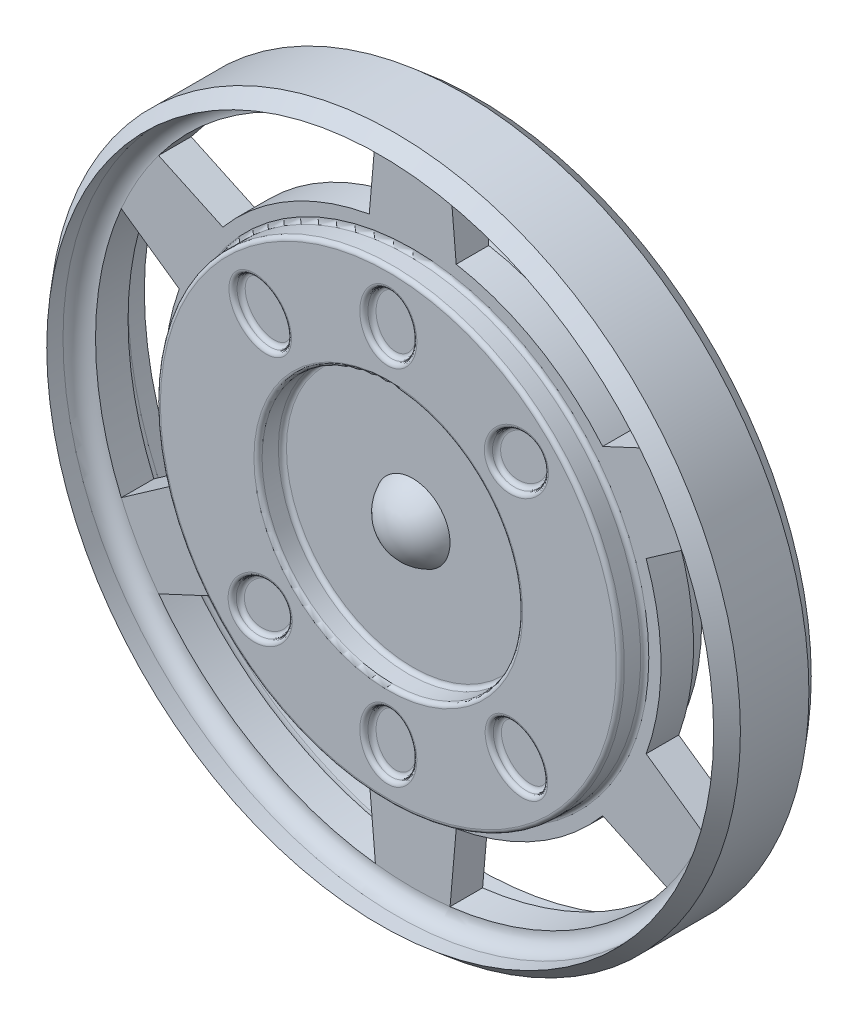
SolidWorks part; units mm, degrees
material "AISI 1020"
ref_plane "Front Plane" through (0, 0, 0) normal (0, 0, 1) x (1, 0, 0)
ref_plane "Top Plane" through (0, 0, 0) normal (0, 1, 0) x (1, 0, 0)
ref_plane "Right Plane" through (0, 0, 0) normal (1, 0, 0) x (0, 0, -1)
sketch "Sketch1" plane through (0, 0, 0) normal (1, 0, 0) x (0, 0, -1)
  line L0 (0, 0) -> (0, 86.3098) construction
  line L33 (-12.7, 0) -> (12.7, 0)
  line L34 (5.08, 11.6397) -> (5.08, 40.7032)
  line L35 (5.08, 40.7032) -> (12.7, 40.7032)
  line L36 (12.7, 40.7032) -> (12.7, 72.4532)
  line L37 (12.7, 72.4532) -> (5.08, 72.4532)
  line L38 (5.08, 72.4532) -> (5.08, 99.06)
  line L39 (10.16, 104.14) -> (15.24, 104.14)
  line L40 (15.24, 104.14) -> (10.6994, 107.95)
  line L41 (10.6994, 107.95) -> (-10.6994, 107.95)
  line L42 (-15.24, 104.14) -> (-10.6994, 107.95)
  line L43 (-10.16, 104.14) -> (-15.24, 104.14)
  line L44 (-5.08, 72.4532) -> (-5.08, 99.06)
  line L45 (-12.7, 72.4532) -> (-5.08, 72.4532)
  line L46 (-12.7, 40.7032) -> (-12.7, 72.4532)
  line L47 (-5.08, 40.7032) -> (-12.7, 40.7032)
  line L48 (-5.08, 11.6397) -> (-5.08, 40.7032)
  arc A4 (12.7, 0) -> (5.08, 11.6397) centre (0, 0) ccw
  arc A5 (5.08, 99.06) -> (10.16, 104.14) centre (10.16, 99.06) cw
  arc A6 (-5.08, 99.06) -> (-10.16, 104.14) centre (-10.16, 99.06) ccw
  arc A7 (-12.7, 0) -> (-5.08, 11.6397) centre (0, 0) cw
  point P2 (0.7835, 0)
  point P17 (0, 107.95)
  dimension "D7" = 5.08
  dimension "D8" = 12.7
  dimension "D1" = 40.7032
  dimension "D2" = 31.75
  dimension "D3" = 40
  dimension "D4" = 10.16
  dimension "D5" = 3.81
  dimension "D6" = 10.16
  dimension "D9" = 107.95
  dimension "D10" = 25.4
revolve "Revolve1" add sketch "Sketch1" angle 360 about L33
sketch "Sketch2" plane through (0, 0, 0) normal (0, 0, 1) x (1, 0, 0)
  line L0 (0, 0) -> (-99.06, 0) construction
  line L1 (-91.0192, 39.0946) -> (-72.898, 26.406)
  line L2 (-91.0192, -39.0946) -> (-72.898, -26.406)
  circle A0 centre (0, 0) radius 99.06 construction
  arc A1 (-91.0192, 39.0946) -> (-91.0192, -39.0946) centre (0, 0) ccw
  circle A3 centre (0, 0) radius 99.06
  arc A4 (-91.0192, 39.0946) -> (-91.0192, -39.0946) centre (0, 0) ccw
  circle A6 centre (0, 0) radius 77.5332
  arc A7 (-72.898, 26.406) -> (-72.898, -26.406) centre (0, 0) ccw
  dimension "D3" = 72.898
  dimension "D4" = 70
  dimension "D2" = 5.08
extrude "Cut-Extrude1" cut sketch "Sketch2" against normal through all both and the other way through all contours A7 L0 A4 L2 | L0 A7 L1 A1
pattern_circular "CirPattern1" count 6 over 360 about axis through (0, 0, 0) along (0, 0, 1) of "Cut-Extrude1"
sketch "Sketch3" plane through (0, 0, 12.7) normal (0, 0, 1) x (1, 0, 0)
  line L0 (0, 40.7032) -> (0, 72.4532) construction
  line L2 (-202.4745, 98.413) -> (-202.04, 98.413) construction
  line L5 (0, 0) -> (0, 72.4532) construction
  line L6 (0, 0) -> (40.0068, 40.0068) construction
  line L7 (0, 0) -> (56.5782, 0) construction
  line L8 (0, 0) -> (-40.0068, -40.0068) construction
  circle A0 centre (0, 0) radius 56.5782 construction
  circle A1 centre (0, 0) radius 40.7032 construction
  circle A2 centre (0, 0) radius 40.7032 construction
  circle A3 centre (0, 0) radius 72.4532 construction
  ellipse E0 centre (-40.0068, 40.0068) end of major axis (-46.2732, 47.1803) minor radius 7.62
  ellipse E2 centre (40.0068, -40.0068) end of major axis (46.2732, -47.1803) minor radius 7.62
  point P14 (0, 56.5782)
extrude "Cut-Extrude2" cut sketch "Sketch3" against normal blind 2.54
pattern_circular "CirPattern2" count 3 every 45 about axis through (0, 0, 12.7) along (0, 0, 1) of "Cut-Extrude2"
mirror "Mirror1" about plane through (0, 0, 0) normal (0, 0, 1) of "CirPattern2", "Cut-Extrude2"
fillet "Fillet4" radius 1.27 16 edges at (-0.6414, -66.0816, 10.16) (-47.1803, -46.2732, 12.7) (-47.1803, -46.2732, 10.16) (46.2732, -47.1803, 12.7) (46.2732, -47.1803, 10.16) (-0.6414, -66.0816, 12.7) (72.4532, 0, 5.08) (72.4532, 0, 12.7) (47.1803, 46.2732, 10.16) (47.1803, 46.2732, 12.7) (0.6414, 66.0816, 12.7) (0.6414, 66.0816, 10.16) (-46.2732, 47.1803, 10.16) (-46.2732, 47.1803, 12.7) (40.7032, 0, 5.08) (40.7032, 0, 12.7)
equation "\"A\" = 4.25"
equation "\"B\" = 1"
equation "\"C\" = 70"
equation "\"D\" = 2.87"
equation "\"E\" = 45"
equation "\"F\" = .75"
equation "\"D9@Sketch1\"=\"A\""
equation "\"D10@Sketch1\"=\"B\""
equation "\"D3@Sketch2\"=\"D\""
equation "\"D4@Sketch2\"=\"C\""
